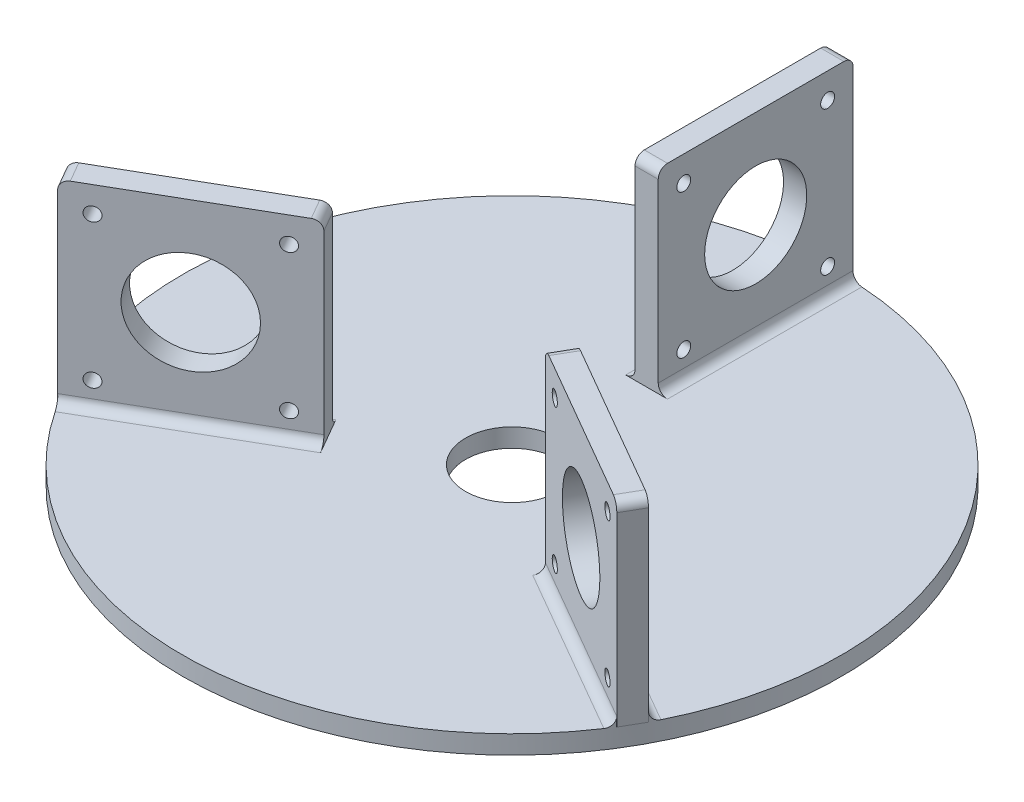
SolidWorks part; units mm, degrees
ref_plane "Front Plane" through (0, 0, 0) normal (0, 0, 1) x (1, 0, 0)
ref_plane "Top Plane" through (0, 0, 0) normal (0, 1, 0) x (1, 0, 0)
ref_plane "Right Plane" through (0, 0, 0) normal (1, 0, 0) x (0, 0, -1)
sketch "Croquis1" plane through (0, 0, 0) normal (0, 1, 0) x (1, 0, 0)
  circle A0 centre (0, 0) radius 10
  circle A1 centre (0, 0) radius 71
  dimension "D1" = 20
  dimension "D2" = 142
extrude "Saliente-Extruir1" add sketch "Croquis1" along normal blind 4
sketch "Croquis3" plane through (0, 4, 0) normal (0, 1, 0) x (1, 0, 0)
  line L0 (60.2378, -37.6651) -> (62.7378, -33.3349)
  line L1 (0, 50) -> (-43.3013, -25) construction
  line L2 (-43.3013, -25) -> (43.3013, -25) construction
  line L3 (43.3013, -25) -> (0, 50) construction
  line L4 (2.5, 29) -> (-2.5, 29)
  line L5 (2.5, 29) -> (2.5, 71)
  line L6 (2.5, 71) -> (-2.5, 71)
  line L7 (-2.5, 29) -> (-2.5, 71)
  line L8 (2.5, 29) -> (-2.5, 71) construction
  line L9 (2.5, 71) -> (-2.5, 29) construction
  line L10 (26.3647, -12.3349) -> (62.7378, -33.3349)
  line L11 (23.8647, -16.6651) -> (26.3647, -12.3349)
  line L12 (23.8647, -16.6651) -> (60.2378, -37.6651)
  line L13 (-62.7378, -33.3349) -> (-60.2378, -37.6651)
  line L14 (-23.8647, -16.6651) -> (-60.2378, -37.6651)
  line L15 (-26.3647, -12.3349) -> (-23.8647, -16.6651)
  line L16 (-26.3647, -12.3349) -> (-62.7378, -33.3349)
  line L17 (-44.5513, -22.8349) -> (-42.0513, -27.1651) construction
  circle A0 centre (0, 0) radius 25 construction
  point P1 (0, 0)
  point P21 (0, 0)
  point P22 (-62.6701, -33.3349)
  point P23 (-57.6872, -42.0828)
  point P24 (0, 0)
  dimension "D1" = 50
  dimension "D2" = 42
  dimension "D3" = 5
  dimension "D4" = 3
extrude "Saliente-Extruir2" add sketch "Croquis3" along normal blind 42
sketch "Croquis4" plane through (1.25, 0, 2.1651) normal (0.5, 0, 0.866) x (0.866, 0, -0.5)
  line L0 (-71, 46) -> (-71, 4) construction
  line L1 (-65.5, 9.5) -> (-34.5, 9.5) construction
  line L2 (-65.5, 9.5) -> (-65.5, 40.5) construction
  line L3 (-65.5, 40.5) -> (-34.5, 40.5) construction
  line L4 (-34.5, 9.5) -> (-34.5, 40.5) construction
  line L5 (-65.5, 9.5) -> (-34.5, 40.5) construction
  line L6 (-65.5, 40.5) -> (-34.5, 9.5) construction
  line L7 (-71, 46) -> (-29, 46) construction
  circle A0 centre (-65.5, 40.5) radius 1.5
  circle A1 centre (-65.5, 9.5) radius 1.5
  circle A2 centre (-34.5, 40.5) radius 1.5
  circle A3 centre (-34.5, 9.5) radius 1.5
  circle A4 centre (-50, 25) radius 11
  point P0 (-50, 25)
  point P7 (-71, 25)
  point P8 (-50, 40.5)
  point P11 (-50, 46)
  dimension "D3" = 3
  dimension "D4" = 22
  dimension "D1" = 31
  dimension "D2" = 31
extrude "Cortar-Extruir1" cut sketch "Croquis4" against normal up to surface (5 mm away) up to face at (-48.181, 20.8, 24.9305)
sketch "Croquis5" plane through (1.25, 0, -2.1651) normal (0.5, 0, -0.866) x (-0.866, 0, -0.5)
  line L0 (-71, 46) -> (-71, 4) construction
  line L1 (-65.5, 9.5) -> (-34.5, 9.5) construction
  line L2 (-65.5, 9.5) -> (-65.5, 40.5) construction
  line L3 (-65.5, 40.5) -> (-34.5, 40.5) construction
  line L4 (-34.5, 9.5) -> (-34.5, 40.5) construction
  line L5 (-65.5, 9.5) -> (-34.5, 40.5) construction
  line L6 (-65.5, 40.5) -> (-34.5, 9.5) construction
  line L7 (-71, 46) -> (-29, 46) construction
  circle A0 centre (-65.5, 40.5) radius 1.5
  circle A1 centre (-34.5, 40.5) radius 1.5
  circle A2 centre (-34.5, 9.5) radius 1.5
  circle A3 centre (-65.5, 9.5) radius 1.5
  circle A4 centre (-50, 25) radius 11
  point P0 (-50, 25)
  point P7 (-71, 25)
  point P8 (-65.5, 25)
  point P11 (-50, 46)
  point P12 (-50, 40.5)
  dimension "D2" = 3
  dimension "D3" = 22
  dimension "D1" = 31
extrude "Cortar-Extruir2" cut sketch "Croquis5" against normal up to surface (5 mm away) up to face at (45.681, 20.8, 29.2607)
sketch "Croquis6" plane through (-2.5, 0, 0) normal (-1, 0, 0) x (0, 0, 1)
  line L0 (-71, 46) -> (-71, 4) construction
  line L1 (-65.5, 9.5) -> (-34.5, 9.5) construction
  line L2 (-65.5, 9.5) -> (-65.5, 40.5) construction
  line L3 (-65.5, 40.5) -> (-34.5, 40.5) construction
  line L4 (-34.5, 9.5) -> (-34.5, 40.5) construction
  line L5 (-65.5, 9.5) -> (-34.5, 40.5) construction
  line L6 (-65.5, 40.5) -> (-34.5, 9.5) construction
  line L7 (-71, 46) -> (-29, 46) construction
  circle A0 centre (-65.5, 40.5) radius 1.5
  circle A1 centre (-34.5, 40.5) radius 1.5
  circle A2 centre (-34.5, 9.5) radius 1.5
  circle A3 centre (-65.5, 9.5) radius 1.5
  circle A4 centre (-50, 25) radius 11
  point P0 (-50, 25)
  point P5 (-65.5, 25)
  point P8 (-71, 25)
  point P9 (-50, 40.5)
  point P12 (-50, 46)
  dimension "D2" = 3
  dimension "D3" = 22
  dimension "D1" = 31
extrude "Cortar-Extruir3" cut sketch "Croquis6" against normal up to surface (5 mm away) up to face at (2.5, 20.8, -54.1912)
fillet "Redondeo1" radius 2 12 edges at (-61.4878, 46, 35.5) (-25.1147, 46, 14.5) (61.4878, 46, 35.5) (25.1147, 46, 14.5) (0, 46, -71) (0, 46, -29) (-2.5, 4, -49.978) (-44.5322, 4, 22.8239) (42.0322, 4, 27.1541) (44.5322, 4, 22.8239) (2.5, 4, -49.978) (-42.0322, 4, 27.1541)
